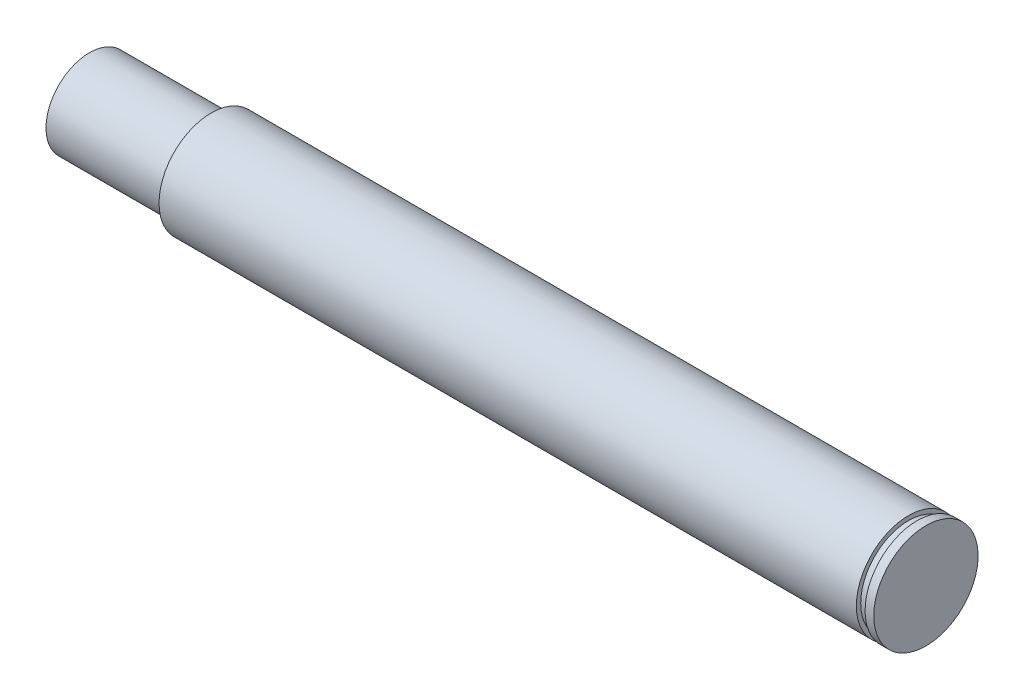
SolidWorks part; units mm, degrees
ref_plane "正面" through (0, 0, 0) normal (0, 0, 1) x (1, 0, 0)
ref_plane "平面" through (0, 0, 0) normal (0, 1, 0) x (1, 0, 0)
ref_plane "右側面" through (0, 0, 0) normal (1, 0, 0) x (0, 0, -1)
sketch "ｽｹｯﾁ2" plane through (0, 0, 0) normal (0, 0, 1) x (1, 0, 0)
  line L0 (0, 5) -> (14, 5)
  line L1 (0, 0) -> (96.2, 0)
  line L2 (0, 0) -> (0, 6)
  line L3 (0, 6) -> (96.2, 6)
  line L4 (96.2, 0) -> (96.2, 6)
  line L5 (48.1, 6) -> (48.1, 0) construction
  line L6 (0, 3) -> (96.2, 3) construction
  line L7 (1, 6) -> (2, 6)
  line L8 (1, 6) -> (1, 5.5)
  line L9 (1, 5.5) -> (2, 5.5)
  line L10 (2, 6) -> (2, 5.5)
  line L11 (1.5, 5.5) -> (1.5, 6) construction
  line L12 (1, 5.75) -> (2, 5.75) construction
  line L13 (94.2, 6) -> (95.2, 6)
  line L14 (94.2, 6) -> (94.2, 5.5)
  line L15 (94.2, 5.5) -> (95.2, 5.5)
  line L16 (95.2, 6) -> (95.2, 5.5)
  line L17 (94.7, 5.5) -> (94.7, 6) construction
  line L18 (94.2, 5.75) -> (95.2, 5.75) construction
  line L19 (14, 5) -> (14, 6)
  point P50 (1.5, 5.75)
  point P64 (48.1, 3)
  point P99 (94.7, 5.75)
  dimension "D1" = 6
  dimension "D2" = 96.2
  dimension "D3" = 1
  dimension "D4" = 0.5
  dimension "D5" = 1
  dimension "D6" = 1
  dimension "D7" = 1
  dimension "D8" = 0.5
  dimension "D9" = 5
  dimension "D10" = 14
revolve "回転1" add sketch "ｽｹｯﾁ2" angle 360 about L1 region at (49.0812, 2.9354, 0)
